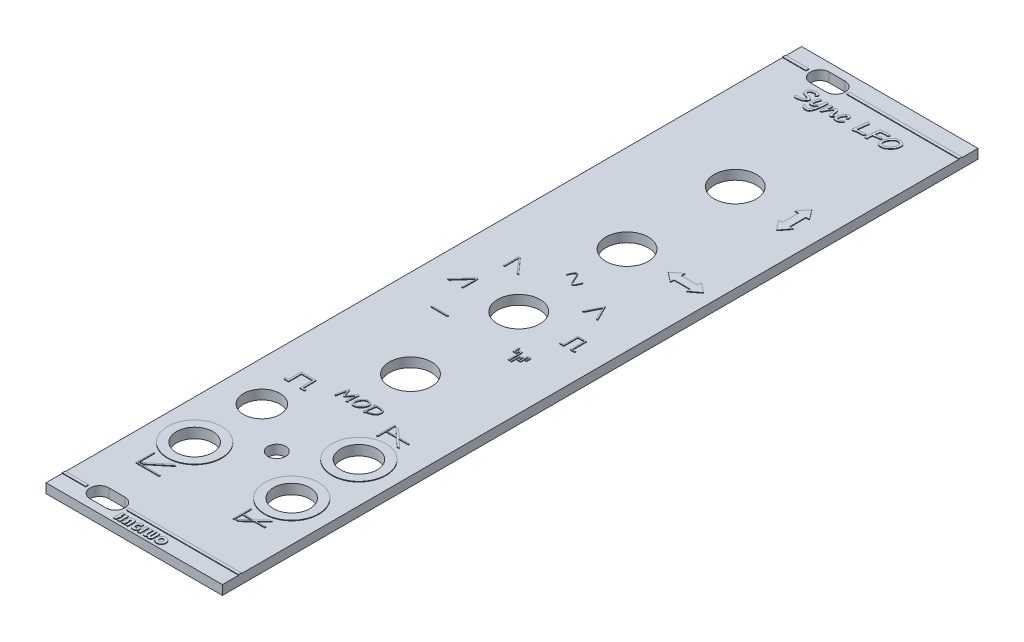
SolidWorks part; units mm, degrees
ref_plane "Ebene vorne" through (0, 0, 0) normal (0, 0, 1) x (1, 0, 0)
ref_plane "Ebene oben" through (0, 0, 0) normal (0, 1, 0) x (1, 0, 0)
ref_plane "Ebene rechts" through (0, 0, 0) normal (1, 0, 0) x (0, 0, -1)
sketch "Skizze2" plane through (0, 0, 0) normal (0, 1, 0) x (1, 0, 0)
  line L0 (-8.9, 61.25) -> (-6.2, 61.25) construction
  line L1 (-15, 64.25) -> (15, 64.25)
  line L2 (-15, 64.25) -> (-15, -64.25)
  line L3 (-15, -64.25) -> (15, -64.25)
  line L4 (15, 64.25) -> (15, -64.25)
  line L5 (0, -64.25) -> (0, 64.25) construction
  line L6 (-15, 0) -> (15, 0) construction
  line L7 (-8.9, 62.85) -> (-6.2, 62.85)
  line L8 (-8.9, 59.65) -> (-6.2, 59.65)
  line L9 (-8.9, -61.25) -> (-6.2, -61.25) construction
  line L10 (-8.9, -59.65) -> (-6.2, -59.65)
  line L11 (-8.9, -62.85) -> (-6.2, -62.85)
  circle A0 centre (-7.55, 61.25) radius 1.6 construction
  circle A1 centre (-7.55, -61.25) radius 1.6 construction
  arc A2 (-8.9, 62.85) -> (-8.9, 59.65) centre (-8.9, 61.25) ccw
  arc A3 (-6.2, 59.65) -> (-6.2, 62.85) centre (-6.2, 61.25) ccw
  arc A4 (-8.9, -59.65) -> (-8.9, -62.85) centre (-8.9, -61.25) ccw
  arc A5 (-6.2, -62.85) -> (-6.2, -59.65) centre (-6.2, -61.25) ccw
  point P10 (-7.55, 61.25)
  point P15 (-4.6, 61.25)
  point P16 (-10.5, 61.25)
  point P19 (-7.55, -61.25)
  point P92 (0, 0)
  dimension "D3" = 3.2
  dimension "D1" = 128.5
  dimension "D2" = 30
  dimension "D4" = 3
  dimension "D5" = 7.45
  dimension "D6" = 3
  dimension "D7" = 5.9
extrude "Aufsatz-Linear austragen1" add sketch "Skizze2" along normal mid plane 1.6
sketch "Skizze3" plane through (0, 0.8, 0) normal (0, 1, 0) x (1, 0, 0)
  line L0 (-15, 64.25) -> (-15, -64.25) construction
  line L1 (-15, 61.5) -> (-11, 61.5)
  line L2 (-15, 61.5) -> (-15, 61)
  line L3 (-15, 61) -> (-11, 61)
  line L4 (-11, 61.5) -> (-11, 61)
  line L5 (-13, 61) -> (-13, 61.5) construction
  line L6 (-15, 61.25) -> (-8.9, 61.25) construction
  line L7 (15, -64.25) -> (15, 64.25) construction
  line L8 (15, 61.5) -> (-4.1, 61.5)
  line L9 (15, 61.5) -> (15, 61)
  line L10 (15, 61) -> (-4.1, 61)
  line L11 (-4.1, 61.5) -> (-4.1, 61)
  line L12 (5.45, 61) -> (5.45, 61.5) construction
  line L13 (15, 61.25) -> (-4.1, 61.25) construction
  line L14 (-8.9, 61.25) -> (-4.1, 61.25) construction
  line L15 (-11, -61.25) -> (-4.1, -61.25) construction
  line L16 (-15, -61) -> (-11, -61)
  line L17 (-15, -61) -> (-15, -61.5)
  line L18 (-15, -61.5) -> (-11, -61.5)
  line L19 (-11, -61) -> (-11, -61.5)
  line L20 (-13, -61.5) -> (-13, -61) construction
  line L21 (-15, -61.25) -> (-11, -61.25) construction
  line L22 (15, -61) -> (-4.1, -61)
  line L23 (15, -61) -> (15, -61.5)
  line L24 (15, -61.5) -> (-4.1, -61.5)
  line L25 (-4.1, -61) -> (-4.1, -61.5)
  line L26 (5.45, -61.5) -> (5.45, -61) construction
  line L27 (15, -61.25) -> (-4.1, -61.25) construction
  line L28 (-15, 56.25) -> (15, 56.25) construction
  line L29 (15, 64.25) -> (-15, 64.25) construction
  line L30 (-15, -63.75) -> (15, -63.75) construction
  line L31 (-15, -64.25) -> (15, -64.25) construction
  arc A3 (-6.2, 59.65) -> (-6.2, 62.85) centre (-6.2, 61.25) ccw construction
  arc A4 (-8.9, 62.85) -> (-8.9, 59.65) centre (-8.9, 61.25) ccw construction
  arc A5 (-6.2, 59.65) -> (-6.2, 62.85) centre (-6.2, 61.25) ccw construction
  arc A6 (-8.9, 62.85) -> (-8.9, 59.65) centre (-8.9, 61.25) ccw construction
  arc A7 (-8.9, 63.35) -> (-8.9, 59.15) centre (-8.9, 61.25) ccw construction
  arc A8 (-6.2, 59.15) -> (-6.2, 63.35) centre (-6.2, 61.25) ccw construction
  arc A10 (-6.2, -62.85) -> (-6.2, -59.65) centre (-6.2, -61.25) ccw construction
  text T0 "Sync LFO" font "Segoe Print" height 2.5
  text T1 "HAGIWO" font "Bauhaus 93" height 1.5
  point P12 (-6.2, 61.25)
  point P25 (-6.2, -61.25)
  point P98 (5.45, 61.25)
  point P112 (-13, -61.25)
  point P128 (-13, 61.25)
  point P181 (5.45, -61.25)
  dimension "D1" = 0.5
  dimension "D2" = 0.5
  dimension "D3" = 8
  dimension "D4" = 0.5
extrude "Aufsatz-Linear austragen2" add sketch "Skizze3" along normal blind 0.1
sketch "Skizze4" plane through (0, 0.8, 0) normal (0, 1, 0) x (1, 0, 0)
  line L1 (-14.605, 50.8) -> (14.605, 50.8) construction
  line L2 (-14.605, 50.8) -> (-14.605, -50.8) construction
  line L3 (-14.605, -50.8) -> (14.605, -50.8) construction
  line L4 (14.605, 50.8) -> (14.605, -50.8) construction
  line L5 (0, -50.8) -> (0, 50.8) construction
  line L6 (-14.605, 0) -> (14.605, 0) construction
  circle A0 centre (0, 37.98) radius 3.6
  circle A1 centre (0, 19.565) radius 3.6
  circle A2 centre (0, 1.15) radius 3.6
  circle A3 centre (0, -17.265) radius 3.6
  circle A4 centre (-8.255, -34.29) radius 3.1
  circle A5 centre (8.255, -34.29) radius 3.1
  circle A6 centre (-8.255, -45.72) radius 3.1
  circle A7 centre (8.255, -45.72) radius 3.1
  circle A8 centre (0, -40.005) radius 1.5
  point P84 (0, 0)
  dimension "D3" = 6.2
  dimension "D4" = 3
  dimension "D5" = 7.2
  dimension "D1" = 29.21
  dimension "D2" = 101.6
  dimension "D6" = 12.82
  dimension "D7" = 31.235
  dimension "D8" = 49.65
  dimension "D9" = 68.065
  dimension "D10" = 85.09
  dimension "D11" = 90.805
  dimension "D12" = 96.52
  dimension "D13" = 6.35
  dimension "D14" = 22.86
extrude "Schnitt-Linear austragen1" cut sketch "Skizze4" against normal through all
sketch "Skizze5" plane through (0, 0.8, 0) normal (0, 1, 0) x (1, 0, 0)
  line L0 (0, 37.98) -> (10, 37.98) construction
  line L1 (10, 40.98) -> (10, 34.98) construction
  line L2 (10, 40.98) -> (8.75, 39.351)
  line L3 (8.75, 39.351) -> (9.375, 39.351)
  line L4 (9.375, 39.351) -> (9.375, 36.609)
  line L5 (10.625, 39.351) -> (10.625, 36.609)
  line L6 (11.25, 39.351) -> (10.625, 39.351)
  line L7 (10, 40.98) -> (11.25, 39.351)
  line L8 (11.25, 36.609) -> (10.625, 36.609)
  line L9 (8.75, 36.609) -> (9.375, 36.609)
  line L10 (10, 34.98) -> (11.25, 36.609)
  line L11 (10, 34.98) -> (8.75, 36.609)
  line L12 (0, 19.565) -> (10, 19.565) construction
  line L13 (10, 20.19) -> (10, 18.94) construction
  line L14 (7, 19.565) -> (8.629, 20.815)
  line L15 (8.629, 20.815) -> (8.629, 20.19)
  line L16 (8.629, 20.19) -> (11.371, 20.19)
  line L17 (11.371, 20.815) -> (11.371, 20.19)
  line L18 (13, 19.565) -> (11.371, 20.815)
  line L19 (13, 19.565) -> (11.371, 18.315)
  line L20 (11.371, 18.315) -> (11.371, 18.94)
  line L21 (8.629, 18.94) -> (11.371, 18.94)
  line L22 (8.629, 18.315) -> (8.629, 18.94)
  line L23 (7, 19.565) -> (8.629, 18.315)
  line L24 (0, -17.265) -> (0, -26.765) construction
  line L25 (-5, -26.765) -> (5, -26.765) construction
  line L26 (-8.255, -34.29) -> (-8.255, -28.79) construction
  line L27 (-10.755, -28.79) -> (-5.755, -28.79) construction
  line L28 (-8.255, -45.72) -> (-8.255, -53.72) construction
  line L29 (-10.005, -28.79) -> (-10.005, -28.49)
  line L30 (7, 1.15) -> (7, 19.565) construction
  line L31 (0, 1.15) -> (0, -5.85) construction
  line L32 (0, 1.15) -> (-4.9497, -3.7997) construction
  line L33 (0, 1.15) -> (4.9497, -3.7997) construction
  line L34 (0, 1.15) -> (-7, 1.15) construction
  line L35 (0, 1.15) -> (-4.9497, 6.0997) construction
  line L36 (0, 1.15) -> (0, 8.15) construction
  line L37 (0, 1.15) -> (4.9497, 6.0997) construction
  line L38 (0, 1.15) -> (7, 1.15) construction
  line L39 (-4.9497, -3.7997) -> (-7, 1.15) construction
  line L40 (-7, 1.15) -> (-4.9497, 6.0997) construction
  line L41 (-4.9497, 6.0997) -> (0, 8.15) construction
  line L42 (0, 8.15) -> (4.9497, 6.0997) construction
  line L43 (4.9497, 6.0997) -> (7, 1.15) construction
  line L44 (7, 1.15) -> (4.9497, -3.7997) construction
  line L45 (-6.7175, -5.5675) -> (-4.9497, -3.7997) construction
  line L46 (-8.2175, -4.0675) -> (-5.2175, -4.0675) construction
  line L47 (-8.2175, -4.0675) -> (-8.2175, -7.0675) construction
  line L48 (-8.2175, -7.0675) -> (-5.2175, -7.0675) construction
  line L49 (-5.2175, -4.0675) -> (-5.2175, -7.0675) construction
  line L50 (-6.7175, -7.0675) -> (-6.7175, -4.0675) construction
  line L51 (-8.2175, -5.5675) -> (-5.2175, -5.5675) construction
  line L52 (-9.5, 1.15) -> (-7, 1.15) construction
  line L53 (-8.1175, -5.4675) -> (-5.3175, -5.4675)
  line L54 (-8.1175, -5.4675) -> (-8.1175, -5.6675)
  line L55 (-8.1175, -5.6675) -> (-5.3175, -5.6675)
  line L56 (-5.3175, -5.4675) -> (-5.3175, -5.6675)
  line L57 (-6.7175, -5.6675) -> (-6.7175, -5.4675) construction
  line L58 (-8.1175, -5.5675) -> (-5.3175, -5.5675) construction
  line L59 (-11, 2.65) -> (-8, 2.65) construction
  line L60 (-11, 2.65) -> (-11, -0.35) construction
  line L61 (-11, -0.35) -> (-8, -0.35) construction
  line L62 (-8, 2.65) -> (-8, -0.35) construction
  line L63 (-9.5, -0.35) -> (-9.5, 2.65) construction
  line L64 (-11, 1.15) -> (-8, 1.15) construction
  line L65 (-10.8, -0.15) -> (-8.4671, 2.45)
  line L66 (-8.4671, 2.45) -> (-8.2, 2.45)
  line L67 (-8.2, 2.45) -> (-8.2, -0.15)
  line L68 (-8.2, -0.15) -> (-8.4, -0.15)
  line L69 (-8.4, -0.15) -> (-8.4, 2.2271)
  line L70 (-8.4, 2.2271) -> (-10.5329, -0.15)
  line L71 (-10.5329, -0.15) -> (-10.8, -0.15)
  line L72 (-9.6336, 1.15) -> (-9.5, 1.0011) construction
  line L73 (-4.9497, 6.0997) -> (-6.7175, 7.8675) construction
  line L74 (-8.2175, 9.3675) -> (-5.2175, 9.3675) construction
  line L75 (-8.2175, 9.3675) -> (-8.2175, 6.3675) construction
  line L76 (-8.2175, 6.3675) -> (-5.2175, 6.3675) construction
  line L77 (-5.2175, 9.3675) -> (-5.2175, 6.3675) construction
  line L78 (-6.7175, 6.3675) -> (-6.7175, 9.3675) construction
  line L79 (-8.2175, 7.8675) -> (-5.2175, 7.8675) construction
  line L80 (-8.0175, 6.5675) -> (-7.8175, 6.5675)
  line L81 (-7.8175, 6.5675) -> (-7.8175, 8.9445)
  line L82 (-7.8175, 8.9445) -> (-5.6861, 6.5675)
  line L83 (-5.6861, 6.5675) -> (-5.4175, 6.5675)
  line L84 (-5.4175, 6.5675) -> (-7.7489, 9.1675)
  line L85 (-7.7489, 9.1675) -> (-8.0175, 9.1675)
  line L86 (-8.0175, 9.1675) -> (-8.0175, 6.5675)
  line L87 (-6.7518, 7.756) -> (-6.6029, 7.8895) construction
  line L88 (0, 10.65) -> (0, 8.15) construction
  line L89 (-1.5, 12.15) -> (1.5, 12.15) construction
  line L90 (-1.5, 12.15) -> (-1.5, 9.15) construction
  line L91 (-1.5, 9.15) -> (1.5, 9.15) construction
  line L92 (1.5, 12.15) -> (1.5, 9.15) construction
  line L93 (0, 9.15) -> (0, 12.15) construction
  line L94 (-1.5, 10.65) -> (1.5, 10.65) construction
  line L95 (4.9497, 6.0997) -> (6.7175, 7.8675) construction
  line L96 (8.2175, 9.3675) -> (5.2175, 9.3675) construction
  line L97 (8.2175, 9.3675) -> (8.2175, 6.3675) construction
  line L98 (8.2175, 6.3675) -> (5.2175, 6.3675) construction
  line L99 (5.2175, 9.3675) -> (5.2175, 6.3675) construction
  line L100 (6.7175, 6.3675) -> (6.7175, 9.3675) construction
  line L101 (8.2175, 7.8675) -> (5.2175, 7.8675) construction
  line L102 (11, 2.65) -> (8, 2.65) construction
  line L103 (11, 2.65) -> (11, -0.35) construction
  line L104 (11, -0.35) -> (8, -0.35) construction
  line L105 (8, 2.65) -> (8, -0.35) construction
  line L106 (9.5, -0.35) -> (9.5, 2.65) construction
  line L107 (11, 1.15) -> (8, 1.15) construction
  line L108 (8.2175, -7.0675) -> (5.2175, -7.0675) construction
  line L109 (8.2175, -7.0675) -> (8.2175, -4.0675) construction
  line L110 (8.2175, -4.0675) -> (5.2175, -4.0675) construction
  line L111 (5.2175, -7.0675) -> (5.2175, -4.0675) construction
  line L112 (6.7175, -4.0675) -> (6.7175, -7.0675) construction
  line L113 (8.2175, -5.5675) -> (5.2175, -5.5675) construction
  line L114 (7, 1.15) -> (9.5, 1.15) construction
  line L115 (4.9497, -3.7997) -> (6.7175, -5.5675) construction
  line L116 (-1.3, 10.75) -> (-1.3, 10.55)
  line L117 (1.3, 10.75) -> (1.3, 10.55)
  line L118 (5.4175, 6.5675) -> (5.6411, 6.5675)
  line L121 (7.7939, 6.5675) -> (8.0175, 6.5675)
  line L122 (8.0175, 6.5675) -> (6.7175, 9.1675)
  line L123 (6.7175, 9.1675) -> (5.4175, 6.5675)
  line L124 (5.6411, 6.5675) -> (6.7175, 8.7203)
  line L125 (6.7175, 8.7203) -> (7.7939, 6.5675)
  line L126 (6.1793, 7.6439) -> (6.0004, 7.7334) construction
  line L127 (8.2, 0.05) -> (8.2, -0.15)
  line L128 (8.2, -0.15) -> (8.95, -0.15)
  line L129 (8.95, -0.15) -> (8.95, 2.25)
  line L130 (8.95, 2.25) -> (10.05, 2.25)
  line L131 (10.05, 2.25) -> (10.05, -0.15)
  line L132 (10.05, -0.15) -> (10.8, -0.15)
  line L133 (10.8, -0.15) -> (10.8, 0.05)
  line L134 (10.8, 0.05) -> (10.25, 0.05)
  line L135 (10.25, 0.05) -> (10.25, 2.45)
  line L136 (10.25, 2.45) -> (8.75, 2.45)
  line L137 (8.75, 2.45) -> (8.75, 0.05)
  line L138 (8.75, 0.05) -> (8.2, 0.05)
  line L139 (8.95, 2.25) -> (8.95, 2.45) construction
  line L140 (8.95, 2.25) -> (8.75, 2.25) construction
  line L141 (5.4175, -4.2675) -> (5.6175, -4.2675)
  line L142 (5.6175, -4.2675) -> (5.6175, -5.0675)
  line L143 (5.6175, -5.0675) -> (5.8175, -5.0675)
  line L144 (5.8175, -5.0675) -> (5.8175, -4.6675)
  line L145 (5.8175, -4.6675) -> (6.4175, -4.6675)
  line L146 (6.4175, -4.6675) -> (6.4175, -6.6675)
  line L147 (6.4175, -6.6675) -> (6.6175, -6.6675)
  line L148 (6.6175, -6.6675) -> (6.6175, -5.3675)
  line L149 (6.6175, -5.3675) -> (7.2175, -5.3675)
  line L150 (7.2175, -5.3675) -> (7.2175, -5.9675)
  line L151 (7.2175, -5.9675) -> (7.4175, -5.9675)
  line L152 (7.4175, -5.9675) -> (7.4175, -4.7675)
  line L153 (7.4175, -4.7675) -> (8.0175, -4.7675)
  line L154 (5.4175, -4.2675) -> (5.4175, -5.2675)
  line L155 (5.4175, -5.2675) -> (6.0175, -5.2675)
  line L156 (6.0175, -5.2675) -> (6.0175, -4.8675)
  line L157 (6.0175, -4.8675) -> (6.2175, -4.8675)
  line L158 (6.2175, -4.8675) -> (6.2175, -6.8675)
  line L159 (6.2175, -6.8675) -> (6.8175, -6.8675)
  line L160 (6.8175, -6.8675) -> (6.8175, -5.5675)
  line L161 (6.8175, -5.5675) -> (7.0175, -5.5675)
  line L162 (7.0175, -5.5675) -> (7.0175, -6.1675)
  line L163 (7.0175, -6.1675) -> (7.6175, -6.1675)
  line L164 (7.6175, -6.1675) -> (7.6175, -4.9675)
  line L165 (7.6175, -4.9675) -> (7.8175, -4.9675)
  line L166 (7.8175, -4.9675) -> (7.8175, -5.5675)
  line L167 (7.8175, -5.5675) -> (8.0175, -5.5675)
  line L168 (8.0175, -5.5675) -> (8.0175, -4.7675)
  line L169 (5.6175, -5.0675) -> (5.6175, -5.2675) construction
  line L170 (6.0175, -4.8675) -> (6.0175, -4.6675) construction
  line L171 (5.4175, -4.2675) -> (5.4175, -6.8675) construction
  line L172 (5.4175, -6.8675) -> (8.0175, -6.8675) construction
  line L173 (6.4175, -6.6675) -> (6.4175, -6.8675) construction
  line L174 (6.8175, -5.5675) -> (6.8175, -5.3675) construction
  line L175 (7.2175, -5.9675) -> (7.2175, -6.1675) construction
  line L176 (7.6175, -4.9675) -> (7.6175, -4.7675) construction
  line L177 (-10.005, -28.49) -> (-9.505, -28.49)
  line L178 (-9.505, -28.49) -> (-9.505, -26.29)
  line L179 (-9.505, -26.29) -> (-7.005, -26.29)
  line L180 (-7.005, -26.29) -> (-7.005, -28.49)
  line L181 (-7.005, -28.49) -> (-6.505, -28.49)
  line L182 (-6.505, -28.49) -> (-6.505, -28.79)
  line L183 (-6.505, -28.79) -> (-7.305, -28.79)
  line L184 (-7.305, -28.79) -> (-7.305, -26.59)
  line L185 (-7.305, -26.59) -> (-9.205, -26.59)
  line L186 (-9.205, -26.59) -> (-9.205, -28.79)
  line L187 (-9.205, -28.79) -> (-10.005, -28.79)
  line L188 (-9.205, -26.59) -> (-9.205, -26.29) construction
  line L189 (-9.205, -26.59) -> (-9.505, -26.59) construction
  line L190 (8.255, -34.29) -> (8.255, -27.79) construction
  line L191 (6.255, -27.79) -> (10.255, -27.79) construction
  line L192 (6.255, -26.29) -> (6.255, -29.29)
  line L193 (6.255, -29.29) -> (6.455, -29.29)
  line L194 (6.455, -29.29) -> (6.455, -27.89)
  line L196 (10.255, -27.89) -> (10.255, -27.69)
  line L198 (6.455, -27.69) -> (6.455, -26.29)
  line L199 (6.455, -26.29) -> (6.255, -26.29)
  line L200 (-7.005, -26.29) -> (-5.755, -26.29) construction
  line L201 (-5.755, -26.29) -> (-5.755, -28.79) construction
  line L202 (6.655, -26.39) -> (7.0918, -26.39)
  line L203 (7.0918, -26.39) -> (8.4676, -27.69)
  line L204 (10.055, -29.19) -> (9.6182, -29.19)
  line L205 (8.4676, -27.69) -> (10.255, -27.69)
  line L206 (10.055, -29.19) -> (8.6792, -27.89)
  line L207 (8.6792, -27.89) -> (10.255, -27.89)
  line L208 (9.6182, -29.19) -> (8.2424, -27.89)
  line L209 (8.2424, -27.89) -> (6.455, -27.89)
  line L210 (6.655, -26.39) -> (8.0308, -27.69)
  line L211 (8.0308, -27.69) -> (6.455, -27.69)
  line L212 (8.9303, -28.54) -> (9.1364, -28.3219) construction
  line L213 (8.255, -45.72) -> (8.255, -52.22) construction
  line L214 (6.255, -52.22) -> (10.255, -52.22) construction
  line L215 (6.255, -50.72) -> (6.455, -50.72)
  line L216 (6.455, -50.72) -> (6.455, -52.12)
  line L217 (6.455, -52.12) -> (8.2424, -52.12)
  line L218 (8.2424, -52.12) -> (9.6182, -50.82)
  line L219 (9.6182, -50.82) -> (10.055, -50.82)
  line L220 (10.055, -50.82) -> (8.6792, -52.12)
  line L221 (8.6792, -52.12) -> (10.255, -52.12)
  line L222 (10.255, -52.12) -> (10.255, -52.32)
  line L223 (10.255, -52.32) -> (8.4676, -52.32)
  line L224 (8.4676, -52.32) -> (7.0918, -53.62)
  line L225 (7.0918, -53.62) -> (6.655, -53.62)
  line L226 (6.655, -53.62) -> (8.0308, -52.32)
  line L227 (8.0308, -52.32) -> (6.455, -52.32)
  line L228 (6.455, -52.32) -> (6.455, -53.72)
  line L229 (6.455, -53.72) -> (6.255, -53.72)
  line L230 (6.255, -53.72) -> (6.255, -50.72)
  line L231 (7.3429, -52.97) -> (7.5489, -53.1881) construction
  line L232 (-10.255, -53.72) -> (-6.255, -53.72) construction
  line L233 (-10.255, -50.72) -> (-10.055, -50.72)
  line L234 (-10.055, -50.72) -> (-10.055, -53.52)
  line L235 (-10.055, -53.52) -> (-6.255, -53.52)
  line L236 (-6.255, -53.52) -> (-6.255, -53.72)
  line L237 (-6.255, -53.72) -> (-10.255, -53.72)
  line L238 (-10.255, -53.72) -> (-10.255, -50.72)
  line L239 (-9.855, -53.32) -> (-9.3837, -53.32)
  line L240 (-9.3837, -53.32) -> (-6.355, -50.82)
  line L241 (-6.355, -50.82) -> (-6.8263, -50.82)
  line L242 (-6.8263, -50.82) -> (-9.855, -53.32)
  line L243 (-8.3406, -52.07) -> (-8.1497, -52.3014) construction
  circle A0 centre (0, 1.15) radius 7 construction
  circle A1 centre (0, 1.15) radius 3.6 construction
  circle A2 centre (-8.255, -45.72) radius 3.1 construction
  circle A3 centre (8.255, -45.72) radius 3.1 construction
  circle A4 centre (8.255, -34.29) radius 3.1 construction
  circle A5 centre (-8.255, -45.72) radius 3.1
  circle A6 centre (8.255, -45.72) radius 3.1
  circle A7 centre (8.255, -34.29) radius 3.1
  circle A8 centre (8.255, -34.29) radius 4.6
  circle A9 centre (8.255, -45.72) radius 4.6
  circle A10 centre (-8.255, -45.72) radius 4.6
  spline S0 degree 4 poles (-1.4924, 10.2016) (-1.4861, 10.2153) (-1.4734, 10.243) (-1.4473, 10.3012) (-1.4039, 10.4002) (-1.2922, 10.6676) (-1.2668, 10.7321) (-1.1312, 11.0538) (-1.0958, 11.1219) (-1.0711, 11.1757) (-1.0522, 11.2142) (-1.0288, 11.2598) (-0.9926, 11.3282) (-0.9465, 11.4068) (-0.8893, 11.491) (-0.834, 11.5561) (-0.7819, 11.6026) (-0.7288, 11.6344) (-0.6785, 11.6514) (-0.6171, 11.6519) (-0.5361, 11.6208) (-0.4202, 11.5172) (-0.2896, 11.3106) (-0.1499, 11.0149) (0, 10.65) (0.1499, 10.2851) (0.2896, 9.9894) (0.4202, 9.7828) (0.5361, 9.6792) (0.617, 9.6481) (0.6902, 9.6487) (0.7613, 9.6799) (0.8264, 9.7351) (0.8805, 9.7986) (0.9232, 9.8589) (0.9652, 9.925) (0.9991, 9.9842) (1.0289, 10.0402) (1.0522, 10.0858) (1.0711, 10.1243) (1.0958, 10.1781) (1.1312, 10.2462) (1.2668, 10.5679) (1.2922, 10.6324) (1.4039, 10.8998) (1.4473, 10.9988) (1.4734, 11.057) (1.4861, 11.0847) (1.4924, 11.0984) knots 0 0 0 0 0 0.010314 0.020629 0.041258 0.082515 0.15963 0.168918 0.178206 0.18285 0.187494 0.196782 0.215358 0.233934 0.249648 0.265362 0.273111 0.28086 0.291368 0.300798 0.313843 0.338236 0.394954 0.464985 0.535015 0.605046 0.661764 0.686157 0.699202 0.708632 0.71914 0.734638 0.750352 0.766066 0.775354 0.784642 0.803218 0.812506 0.81715 0.821794 0.831082 0.84037 0.917485 0.958742 0.979371 0.989686 1 1 1 1 1 construction
  spline S1 degree 4 poles (-1.3, 10.65) (-1.2636, 10.738) (-1.2259, 10.829) (-1.1312, 11.0538) (-1.0958, 11.1219) (-1.0711, 11.1757) (-1.0522, 11.2142) (-1.0288, 11.2598) (-0.9926, 11.3282) (-0.9465, 11.4068) (-0.8893, 11.491) (-0.834, 11.5561) (-0.7819, 11.6026) (-0.7288, 11.6344) (-0.6785, 11.6514) (-0.6171, 11.6519) (-0.5361, 11.6208) (-0.4202, 11.5172) (-0.2896, 11.3106) (-0.1499, 11.0149) (0, 10.65) (0.1499, 10.2851) (0.2896, 9.9894) (0.4202, 9.7828) (0.5361, 9.6792) (0.617, 9.6481) (0.6902, 9.6487) (0.7613, 9.6799) (0.8264, 9.7351) (0.8805, 9.7986) (0.9232, 9.8589) (0.9652, 9.925) (0.9991, 9.9842) (1.0289, 10.0402) (1.0522, 10.0858) (1.0711, 10.1243) (1.0958, 10.1781) (1.1312, 10.2462) (1.2259, 10.471) (1.2636, 10.562) (1.3, 10.65) knots 0.082515 0.082515 0.082515 0.082515 0.082515 0.15963 0.168918 0.178206 0.18285 0.187494 0.196782 0.215358 0.233934 0.249648 0.265362 0.273111 0.28086 0.291368 0.300798 0.313843 0.338236 0.394954 0.464985 0.535015 0.605046 0.661764 0.686157 0.699202 0.708632 0.71914 0.734638 0.750352 0.766066 0.775354 0.784642 0.803218 0.812506 0.81715 0.821794 0.831082 0.84037 0.917485 0.917485 0.917485 0.917485 0.917485 construction
  spline S2 degree 4 poles (-1.4924, 10.3016) (-1.4861, 10.3153) (-1.4734, 10.343) (-1.4473, 10.4012) (-1.4039, 10.5002) (-1.2922, 10.7676) (-1.2668, 10.8321) (-1.1312, 11.1538) (-1.0958, 11.2219) (-1.0711, 11.2757) (-1.0522, 11.3142) (-1.0288, 11.3598) (-0.9926, 11.4282) (-0.9465, 11.5068) (-0.8893, 11.591) (-0.834, 11.6561) (-0.7819, 11.7026) (-0.7288, 11.7344) (-0.6785, 11.7514) (-0.6171, 11.7519) (-0.5361, 11.7208) (-0.4202, 11.6172) (-0.2896, 11.4106) (-0.1499, 11.1149) (0, 10.75) (0.1499, 10.3851) (0.2896, 10.0894) (0.4202, 9.8828) (0.5361, 9.7792) (0.617, 9.7481) (0.6902, 9.7487) (0.7613, 9.7799) (0.8264, 9.8351) (0.8805, 9.8986) (0.9232, 9.9589) (0.9652, 10.025) (0.9991, 10.0842) (1.0289, 10.1402) (1.0522, 10.1858) (1.0711, 10.2243) (1.0958, 10.2781) (1.1312, 10.3462) (1.2668, 10.6679) (1.2922, 10.7324) (1.4039, 10.9998) (1.4473, 11.0988) (1.4734, 11.157) (1.4861, 11.1847) (1.4924, 11.1984) knots 0 0 0 0 0 0.010314 0.020629 0.041258 0.082515 0.15963 0.168918 0.178206 0.18285 0.187494 0.196782 0.215358 0.233934 0.249648 0.265362 0.273111 0.28086 0.291368 0.300798 0.313843 0.338236 0.394954 0.464985 0.535015 0.605046 0.661764 0.686157 0.699202 0.708632 0.71914 0.734638 0.750352 0.766066 0.775354 0.784642 0.803218 0.812506 0.81715 0.821794 0.831082 0.84037 0.917485 0.958742 0.979371 0.989686 1 1 1 1 1 construction
  spline S3 degree 4 poles (-1.3, 10.75) (-1.2636, 10.838) (-1.2259, 10.929) (-1.1312, 11.1538) (-1.0958, 11.2219) (-1.0711, 11.2757) (-1.0522, 11.3142) (-1.0288, 11.3598) (-0.9926, 11.4282) (-0.9465, 11.5068) (-0.8893, 11.591) (-0.834, 11.6561) (-0.7819, 11.7026) (-0.7288, 11.7344) (-0.6785, 11.7514) (-0.6171, 11.7519) (-0.5361, 11.7208) (-0.4202, 11.6172) (-0.2896, 11.4106) (-0.1499, 11.1149) (0, 10.75) (0.1499, 10.3851) (0.2896, 10.0894) (0.4202, 9.8828) (0.5361, 9.7792) (0.617, 9.7481) (0.6902, 9.7487) (0.7613, 9.7799) (0.8264, 9.8351) (0.8805, 9.8986) (0.9232, 9.9589) (0.9652, 10.025) (0.9991, 10.0842) (1.0289, 10.1402) (1.0522, 10.1858) (1.0711, 10.2243) (1.0958, 10.2781) (1.1312, 10.3462) (1.2259, 10.571) (1.2636, 10.662) (1.3, 10.75) knots 0.082515 0.082515 0.082515 0.082515 0.082515 0.15963 0.168918 0.178206 0.18285 0.187494 0.196782 0.215358 0.233934 0.249648 0.265362 0.273111 0.28086 0.291368 0.300798 0.313843 0.338236 0.394954 0.464985 0.535015 0.605046 0.661764 0.686157 0.699202 0.708632 0.71914 0.734638 0.750352 0.766066 0.775354 0.784642 0.803218 0.812506 0.81715 0.821794 0.831082 0.84037 0.917485 0.917485 0.917485 0.917485 0.917485
  spline S4 degree 4 poles (-1.4924, 10.1016) (-1.4861, 10.1153) (-1.4734, 10.143) (-1.4473, 10.2012) (-1.4039, 10.3002) (-1.2922, 10.5676) (-1.2668, 10.6321) (-1.1312, 10.9538) (-1.0958, 11.0219) (-1.0711, 11.0757) (-1.0522, 11.1142) (-1.0288, 11.1598) (-0.9926, 11.2282) (-0.9465, 11.3068) (-0.8893, 11.391) (-0.834, 11.4561) (-0.7819, 11.5026) (-0.7288, 11.5344) (-0.6785, 11.5514) (-0.6171, 11.5519) (-0.5361, 11.5208) (-0.4202, 11.4172) (-0.2896, 11.2106) (-0.1499, 10.9149) (0, 10.55) (0.1499, 10.1851) (0.2896, 9.8894) (0.4202, 9.6828) (0.5361, 9.5792) (0.617, 9.5481) (0.6902, 9.5487) (0.7613, 9.5799) (0.8264, 9.6351) (0.8805, 9.6986) (0.9232, 9.7589) (0.9652, 9.825) (0.9991, 9.8842) (1.0289, 9.9402) (1.0522, 9.9858) (1.0711, 10.0243) (1.0958, 10.0781) (1.1312, 10.1462) (1.2668, 10.4679) (1.2922, 10.5324) (1.4039, 10.7998) (1.4473, 10.8988) (1.4734, 10.957) (1.4861, 10.9847) (1.4924, 10.9984) knots 0 0 0 0 0 0.010314 0.020629 0.041258 0.082515 0.15963 0.168918 0.178206 0.18285 0.187494 0.196782 0.215358 0.233934 0.249648 0.265362 0.273111 0.28086 0.291368 0.300798 0.313843 0.338236 0.394954 0.464985 0.535015 0.605046 0.661764 0.686157 0.699202 0.708632 0.71914 0.734638 0.750352 0.766066 0.775354 0.784642 0.803218 0.812506 0.81715 0.821794 0.831082 0.84037 0.917485 0.958742 0.979371 0.989686 1 1 1 1 1 construction
  spline S5 degree 4 poles (-1.3, 10.55) (-1.2636, 10.638) (-1.2259, 10.729) (-1.1312, 10.9538) (-1.0958, 11.0219) (-1.0711, 11.0757) (-1.0522, 11.1142) (-1.0288, 11.1598) (-0.9926, 11.2282) (-0.9465, 11.3068) (-0.8893, 11.391) (-0.834, 11.4561) (-0.7819, 11.5026) (-0.7288, 11.5344) (-0.6785, 11.5514) (-0.6171, 11.5519) (-0.5361, 11.5208) (-0.4202, 11.4172) (-0.2896, 11.2106) (-0.1499, 10.9149) (0, 10.55) (0.1499, 10.1851) (0.2896, 9.8894) (0.4202, 9.6828) (0.5361, 9.5792) (0.617, 9.5481) (0.6902, 9.5487) (0.7613, 9.5799) (0.8264, 9.6351) (0.8805, 9.6986) (0.9232, 9.7589) (0.9652, 9.825) (0.9991, 9.8842) (1.0289, 9.9402) (1.0522, 9.9858) (1.0711, 10.0243) (1.0958, 10.0781) (1.1312, 10.1462) (1.2259, 10.371) (1.2636, 10.462) (1.3, 10.55) knots 0.082515 0.082515 0.082515 0.082515 0.082515 0.15963 0.168918 0.178206 0.18285 0.187494 0.196782 0.215358 0.233934 0.249648 0.265362 0.273111 0.28086 0.291368 0.300798 0.313843 0.338236 0.394954 0.464985 0.535015 0.605046 0.661764 0.686157 0.699202 0.708632 0.71914 0.734638 0.750352 0.766066 0.775354 0.784642 0.803218 0.812506 0.81715 0.821794 0.831082 0.84037 0.917485 0.917485 0.917485 0.917485 0.917485
  text T0 "MOD" font "Segoe Print" height 2
  point P13 (10.625, 37.98)
  point P14 (9.375, 37.98)
  point P177 (6.6175, -5.5675)
  point P200 (-6.7175, 7.8675)
  point P217 (-6.7175, -5.5675)
  point P219 (0, 10.65)
  point P221 (6.7175, 7.8675)
  point P238 (9.5, 1.15)
  point P246 (-9.5, 1.15)
  point P248 (6.7175, -5.5675)
  point P292 (-6.7175, -5.5675)
  point P306 (0, 0)
  dimension "D1" = 75
  dimension "D2" = 1.25
  dimension "D3" = 2.5
  dimension "D4" = 75
  dimension "D5" = 6
  dimension "D6" = 7
  dimension "D7" = 9.5
  dimension "D8" = 10
  dimension "D9" = 5.5
  dimension "D10" = 5
  dimension "D11" = 270
  dimension "D12" = 3
  dimension "D13" = 2.5
  dimension "D14" = 0.2
  dimension "D15" = 0.2
  dimension "D16" = 0.2
  dimension "D17" = 0.2
  dimension "D18" = 0.2
  dimension "D19" = 0.2
  dimension "D20" = 0.2
  dimension "D21" = 0.2
  dimension "D22" = 0.2
  dimension "D23" = 0.2
  dimension "D24" = 0.2
  dimension "D25" = 0.2
  dimension "D26" = 0.2
  dimension "D27" = 0.1
  dimension "D28" = 0.1
  dimension "D29" = 0.2
  dimension "D30" = 0.2
  dimension "D31" = 0.2
  dimension "D32" = 0.2
  dimension "D33" = 0.2
  dimension "D34" = 0.2
  dimension "D35" = 0.2
  dimension "D36" = 0.2
  dimension "D37" = 0.2
  dimension "D38" = 0.2
  dimension "D39" = 1.5
  dimension "D40" = 0.2
  dimension "D41" = 0.2
  dimension "D42" = 0.2
  dimension "D43" = 0.2
  dimension "D44" = 0.6
  dimension "D45" = 1
  dimension "D46" = 0.4
  dimension "D47" = 0.6
  dimension "D48" = 1.2
  dimension "D49" = 0.3
  dimension "D50" = 2.5
  dimension "D51" = 3.5
  dimension "D52" = 2.5
  dimension "D54" = 0.2
  dimension "D55" = 3
  dimension "D56" = 4
  dimension "D57" = 0.2
  dimension "D58" = 0.2
  dimension "D59" = 0.1
  dimension "D60" = 0.1
  dimension "D61" = 0.3
  dimension "D62" = 6.5
  dimension "D63" = 0.1
  dimension "D64" = 0.2
  dimension "D65" = 0.1
  dimension "D66" = 0.2
  dimension "D67" = 0.1
  dimension "D68" = 0.1
  dimension "D69" = 0.2
  dimension "D70" = 0.2
  dimension "D53" = 1.5
extrude "Aufsatz-Linear austragen3" add sketch "Skizze5" along normal blind 0.1
